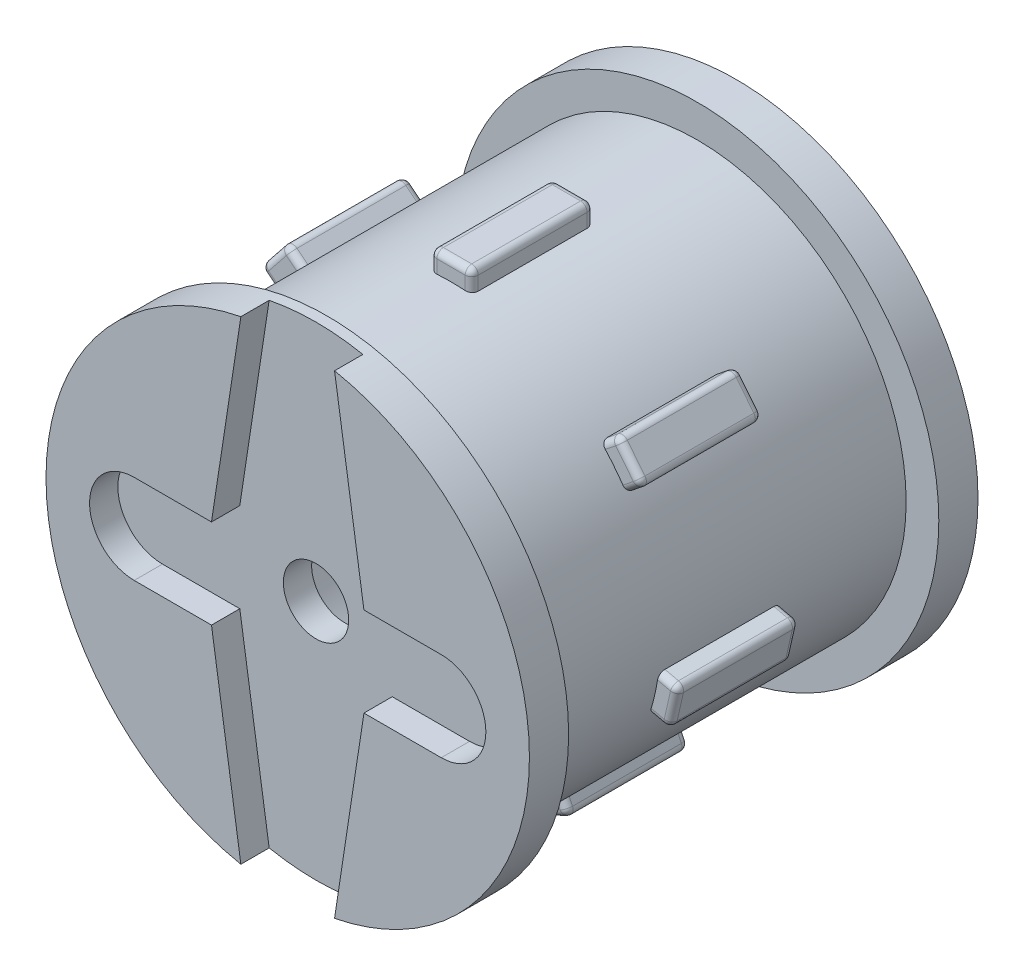
SolidWorks part; units mm, degrees
ref_plane "Ebene vorne" through (0, 0, 0) normal (0, 0, 1) x (1, 0, 0)
ref_plane "Ebene oben" through (0, 0, 0) normal (0, 1, 0) x (1, 0, 0)
ref_plane "Ebene rechts" through (0, 0, 0) normal (1, 0, 0) x (0, 0, -1)
sketch "Skizze1" plane through (0, 0, 0) normal (0, 0, 1) x (1, 0, 0)
  circle A0 centre (0, 0) radius 9.6
  dimension "D1" = 19.2
extrude "Aufsatz-Linear austragen1" add sketch "Skizze1" along normal blind 10.3 and the other way blind 10.3
ref_axis "Rotationsachse" through (0, 0, -10.3) along (0, 0, 1)
sketch "Skizze2" plane through (0, 0, 10.3) normal (0, 0, 1) x (1, 0, 0)
  circle A0 centre (0, 0) radius 11.1
  dimension "D1" = 22.2
extrude "Aufsatz-Linear austragen2" add sketch "Skizze2" against normal blind 1.8
sketch "Skizze3" plane through (0, 0, -10.3) normal (0, 0, -1) x (-1, 0, 0)
  circle A0 centre (0, 0) radius 11.1
  dimension "D1" = 22.2
extrude "Aufsatz-Linear austragen3" add sketch "Skizze3" against normal blind 1.8
sketch "Skizze12" plane through (0, 0, 10.3) normal (0, 0, 1) x (1, 0, 0)
  line L0 (3.5, -2.05) -> (1.25, -16.8)
  line L1 (-3.05, 2.05) -> (3.05, 2.05)
  line L2 (-3.05, 2.05) -> (-3.05, -2.05)
  line L3 (-3.05, -2.05) -> (3.05, -2.05)
  line L4 (3.05, 2.05) -> (3.05, -2.05)
  line L5 (-3.05, 2.05) -> (3.05, -2.05) construction
  line L6 (-3.05, -2.05) -> (3.05, 2.05) construction
  line L7 (3.05, 2.05) -> (7.05, 2.05)
  line L8 (3.05, 2.05) -> (3.05, -2.05)
  line L9 (3.05, -2.05) -> (7.05, -2.05)
  line L10 (7.05, 2.05) -> (7.05, -2.05)
  line L11 (-3.05, -2.05) -> (-3.5, -2.05)
  line L12 (-3.5, -2.05) -> (-1.25, -16.8)
  circle A0 centre (7.05, 0) radius 2.05
  circle A1 centre (0, -16.8) radius 1.25
  point P0 (0, 0)
  point P12 (0, -2.05)
  circle M11 centre (0, 0) radius 11.1
  dimension "D5" = 2.5
  dimension "D1" = 6.1
  dimension "D2" = 4.1
  dimension "D3" = 4
  dimension "D4" = 14.75
  dimension "D6" = 3.05
  dimension "D7" = 3.5
  dimension "D8" = 3.5
extrude "Schnitt-Linear austragen1" cut sketch "Skizze12" against normal blind 1.3 contours A1 | A1 L0 L12 M11 | L11 L12 L0 L9 L3 M11 | L4 L1 L2 L3 | A0 L7 L4 L9 | L10 A0 | L10 A0 region at (0, -6.1763, 10.3) region at (4.2888, 0, 10.3) region at (0, -13.2896, 10.3) region at (0, 0, 10.3) region at (6.18, 0, 10.3) region at (7.92, 0, 10.3) region at (0, -16.8, 10.3)
sketch "Skizze8" plane through (0, 0, 0) normal (1, 0, 0) x (0, 0, -1)
  line L0 (10.3, 0) -> (10.3, 8)
  line L1 (10.3, -11.1) -> (10.3, 11.1) construction
  line L2 (10.3, 8) -> (8.5, 8)
  line L3 (8.5, 11.1) -> (8.5, -11.1) construction
  line L4 (8.5, 8) -> (-7.7, 3.5)
  line L6 (-7.7, 3.5) -> (-7.7, 0)
  line L7 (-7.7, 0) -> (10.3, 0)
  dimension "D1" = 8
  dimension "D2" = 3.5
  dimension "D3" = 18
revolve "Schnitt-Rotation1" cut sketch "Skizze8" angle 360 about axis through (0, 0, -10.3) along (0, 0, 1)
ref_plane "Schnittebene_Zaehne" through (0, 0, 0) normal (0, 0, -1) x (-1, 0, 0)
sketch "Skizze11" plane through (0, 0, 0) normal (0, 0, -1) x (-1, 0, 0)
  line L0 (0, 0) -> (0, 12.664) construction
  line L6 (-0.95, 8.71) -> (0.95, 8.71)
  line L7 (-0.95, 8.71) -> (-0.95, 10.49)
  line L8 (-0.95, 10.49) -> (0.95, 10.49)
  line L9 (0.95, 8.71) -> (0.95, 10.49)
  line L10 (-0.95, 8.71) -> (0.95, 10.49) construction
  line L11 (-0.95, 10.49) -> (0.95, 8.71) construction
  circle A1 centre (0, 0) radius 9.6 construction
  point P3 (0, 9.6)
  dimension "D1" = 0.89
  dimension "D2" = 1.9
extrude "Aufsatz-Linear austragen4" add sketch "Skizze11" along normal blind 2.8 and the other way blind 2.8
pattern_circular "Kreismuster2" count 7 over 360 about axis through (0, 0, -10.3) along (0, 0, 1) of "Aufsatz-Linear austragen4"
fillet "Verrundung1" radius 0.3 56 edges at (8.2014, 6.5404, 2.8) (7.6091, 7.2831, 0) (8.2014, 6.5404, -2.8) (8.7937, 5.7977, 0) (-8.4274, 5.5055, 2.8) (-7.2428, 6.991, 2.8) (-7.2428, 6.991, -2.8) (-8.4274, 5.5055, -2.8) (-9.5588, -3.1562, -2.8) (-9.9816, -1.3038, -2.8) (-9.5588, -3.1562, 2.8) (-9.9816, -1.3038, 2.8) (-5.2041, -8.6168, -2.8) (-3.4922, -9.4412, -2.8) (-3.4922, -9.4412, 2.8) (-5.2041, -8.6168, 2.8) (5.2041, -8.6168, 2.8) (3.4922, -9.4412, 2.8) (3.4922, -9.4412, -2.8) (5.2041, -8.6168, -2.8) (9.5588, -3.1562, 2.8) (9.5588, -3.1562, -2.8) (9.9816, -1.3038, 2.8) (9.9816, -1.3038, -2.8) (8.4274, 5.5055, 2.8) (8.4274, 5.5055, -2.8) (7.2428, 6.991, -2.8) (7.2428, 6.991, 2.8) (0.95, 10.0214, 2.8) (0.95, 10.0214, -2.8) (-0.95, 10.0214, -2.8) (-0.95, 10.0214, 2.8) (10.4384, -1.4081, 0) (10.227, -2.3342, 2.8) (10.227, -2.3342, -2.8) (10.0156, -3.2604, 0) (4.5514, -9.4512, 2.8) (4.5514, -9.4512, -2.8) (5.4074, -9.039, 0) (3.6955, -9.8634, 0) (-4.5514, -9.4512, 2.8) (-4.5514, -9.4512, -2.8) (-5.4074, -9.039, 0) (-3.6955, -9.8634, 0) (-10.227, -2.3342, 2.8) (-10.227, -2.3342, -2.8) (-10.0156, -3.2604, 0) (-10.4384, -1.4081, 0) (-8.2014, 6.5404, -2.8) (-8.2014, 6.5404, 2.8) (-8.7937, 5.7977, 0) (-7.6091, 7.2831, 0) (0, 10.49, -2.8) (0, 10.49, 2.8) (0.95, 10.49, 0) (-0.95, 10.49, 0)
pattern_circular "Kreismuster3" count 2 over 360 about axis through (0, 0, -10.3) along (0, 0, 1) of "Schnitt-Linear austragen1"
sketch "Skizze14" plane through (0, 0, 10.3) normal (0, 0, 1) x (1, 0, 0)
  circle A0 centre (0, 0) radius 1.5
  dimension "D1" = 3
extrude "Schnitt-Linear austragen2" cut sketch "Skizze14" against normal up to surface (2.6 mm away) up to face at (-3.5, 0, 7.7)
